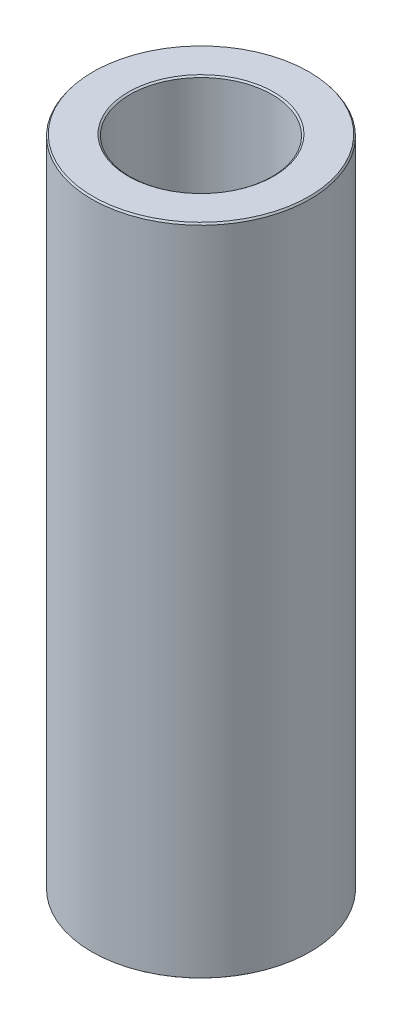
SolidWorks part; units mm, degrees
ref_plane "Front Plane" through (0, 0, 0) normal (0, 0, 1) x (1, 0, 0)
ref_plane "Top Plane" through (0, 0, 0) normal (0, 1, 0) x (1, 0, 0)
ref_plane "Right Plane" through (0, 0, 0) normal (1, 0, 0) x (0, 0, -1)
sketch "Sketch1" plane through (0, 0, 0) normal (0, 1, 0) x (1, 0, 0)
  circle A0 centre (0, 0) radius 50
  dimension "SLEEVE_OD" = 100
extrude "Boss-Extrude1" add sketch "Sketch1" along normal blind 299.634
sketch "Sketch2" plane through (0, 0, 0) normal (0, 1, 0) x (1, 0, 0)
  circle A0 centre (0, 0) radius 32.557
  dimension "BORE_D" = 65.114
extrude "Cut-Extrude1" cut sketch "Sketch2" along normal through all
chamfer "Chamfer1" distance 0.7827 angle 36.508 4 edges at (0, 299.634, 32.557) (0, 0, 32.557) (0, 0, 50) (0, 299.634, 50) first distance on face at (0, 299.634, 32.557) first distance on face at (0, 0, 32.557) first distance on face at (0, 299.634, 50)
